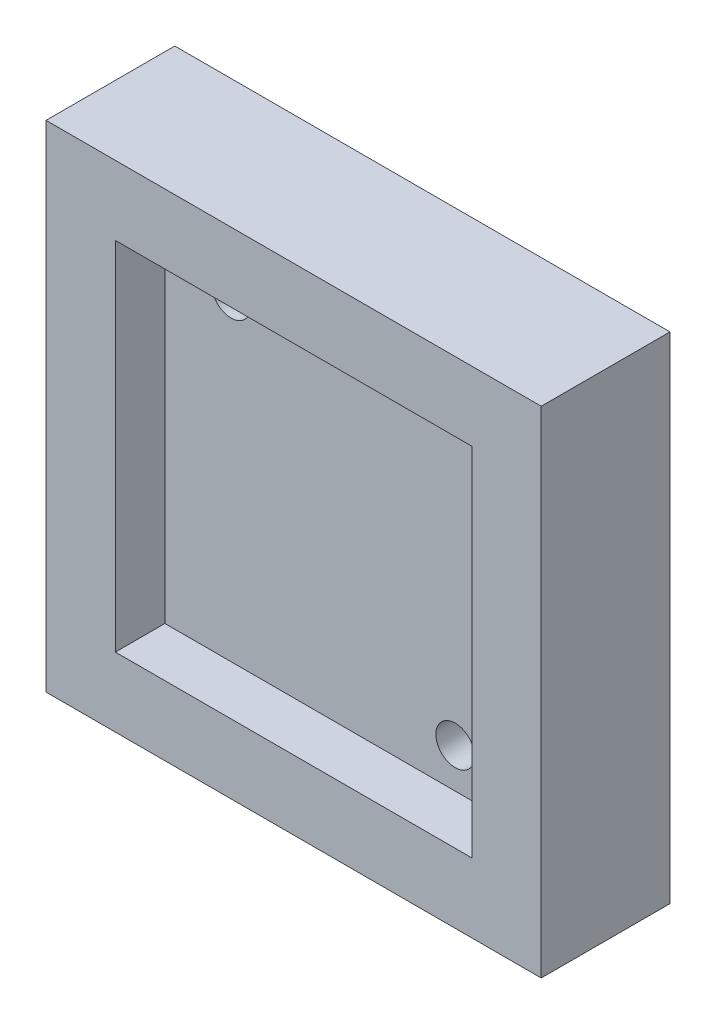
SolidWorks part; units mm, degrees
ref_plane "Plan de face" through (0, 0, 0) normal (0, 0, 1) x (1, 0, 0)
ref_plane "Plan de dessus" through (0, 0, 0) normal (0, 1, 0) x (1, 0, 0)
ref_plane "Plan de droite" through (0, 0, 0) normal (1, 0, 0) x (0, 0, -1)
sketch "Esquisse1" plane through (0, 0, 0) normal (0, 0, 1) x (1, 0, 0)
  line L1 (-25, -25) -> (25, -25)
  line L2 (-25, -25) -> (-25, 25)
  line L3 (-25, 25) -> (25, 25)
  line L4 (25, -25) -> (25, 25)
  line L5 (-25, -25) -> (25, 25) construction
  line L6 (-25, 25) -> (25, -25) construction
  point P0 (0, 0)
  dimension "D1" = 50
extrude "Boss.-Extru.1" add sketch "Esquisse1" along normal blind 6.5 and the other way blind 6.5
sketch "Esquisse2" plane through (0, 0, 6.5) normal (0, 0, 1) x (1, 0, 0)
  line L0 (25, 25) -> (-25, 25) construction
  line L1 (18, -18) -> (-18, -18)
  line L2 (18, -18) -> (18, 18)
  line L3 (18, 18) -> (-18, 18)
  line L4 (-18, -18) -> (-18, 18)
  line L5 (18, -18) -> (-18, 18) construction
  line L6 (18, 18) -> (-18, -18) construction
  line L7 (-25, 25) -> (-25, -25) construction
  point P0 (0, 0)
  dimension "D1" = 7
  dimension "D2" = 7
extrude "Enlèv. mat.-Extru.1" cut sketch "Esquisse2" against normal blind 5
sketch "Esquisse3" plane through (0, 0, -6.5) normal (0, 0, -1) x (-1, 0, 0)
  line L0 (25, -25) -> (-25, -25) construction
  line L1 (18, 18) -> (-18, 18)
  line L2 (18, 18) -> (18, -18)
  line L3 (18, -18) -> (-18, -18)
  line L4 (-18, 18) -> (-18, -18)
  line L5 (18, 18) -> (-18, -18) construction
  line L6 (18, -18) -> (-18, 18) construction
  line L7 (25, 25) -> (25, -25) construction
  point P0 (0, 0)
  dimension "D1" = 7
  dimension "D2" = 7
extrude "Enlèv. mat.-Extru.2" cut sketch "Esquisse3" against normal blind 5
sketch "Esquisse4" plane through (0, 0, 1.5) normal (0, 0, 1) x (1, 0, 0)
  line L1 (-11.3137, -14) -> (11.3137, -14)
  line L2 (-11.3137, -14) -> (-11.3137, 14)
  line L3 (-11.3137, 14) -> (11.3137, 14)
  line L4 (11.3137, -14) -> (11.3137, 14)
  line L5 (-11.3137, -14) -> (11.3137, 14) construction
  line L6 (-11.3137, 14) -> (11.3137, -14) construction
  point P0 (0, 0)
  dimension "D1" = 36
  dimension "D2" = 28
hole_wizard "Dégagement M3.51" positions "Esquisse6" profile "Esquisse7" hole size "M3.5" standard "Iso" end condition through all
sketch "Esquisse6" plane through (0, 0, 1.5) normal (0, 0, 1) x (1, 0, 0)
  point P0 (-11.3137, 14)
  point P3 (11.3137, -14)
sketch "Esquisse7" plane through (-11.3137, 14, 1.5) normal (1, 0, 0) x (0, -1, 0)
  line L0 (0, 0) -> (0, 8)
  line L1 (0, 8) -> (1.95, 8)
  line L2 (1.95, 8) -> (1.95, 0)
  line L5 (1.95, 0) -> (0, 0)
  line L11 (0, -6.35) -> (0, 107.95) construction
  dimension "Diamètre du perçage jusqu'au prochain" = 3.9
  dimension "Profondeur du perçage jusqu'au prochain" = 8
